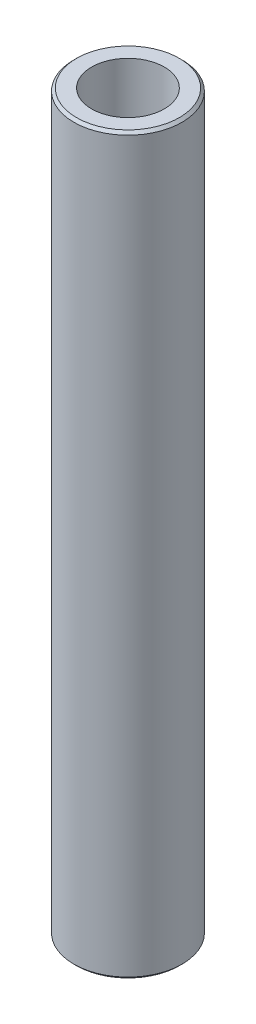
SolidWorks part; units mm, degrees
ref_plane "Front Plane" through (0, 0, 0) normal (0, 0, 1) x (1, 0, 0)
ref_plane "Top Plane" through (0, 0, 0) normal (0, 1, 0) x (1, 0, 0)
ref_plane "Right Plane" through (0, 0, 0) normal (1, 0, 0) x (0, 0, -1)
sketch "Sketch1" plane through (0, 0, 0) normal (0, 1, 0) x (1, 0, 0)
  circle A0 centre (0, 0) radius 17.5
  dimension "SHAFT_OD" = 35
extrude "Boss-Extrude1" add sketch "Sketch1" along normal blind 237.6535
sketch "Sketch2" plane through (0, 0, 0) normal (0, 1, 0) x (1, 0, 0)
  circle A0 centre (0, 0) radius 11.7616
  dimension "BORE_D" = 23.5232
extrude "Cut-Extrude1" cut sketch "Sketch2" along normal through all
chamfer "Chamfer1" distance 0.8685 angle 45 2 edges at (0, 237.6535, 17.5) (0, 0, 17.5)
